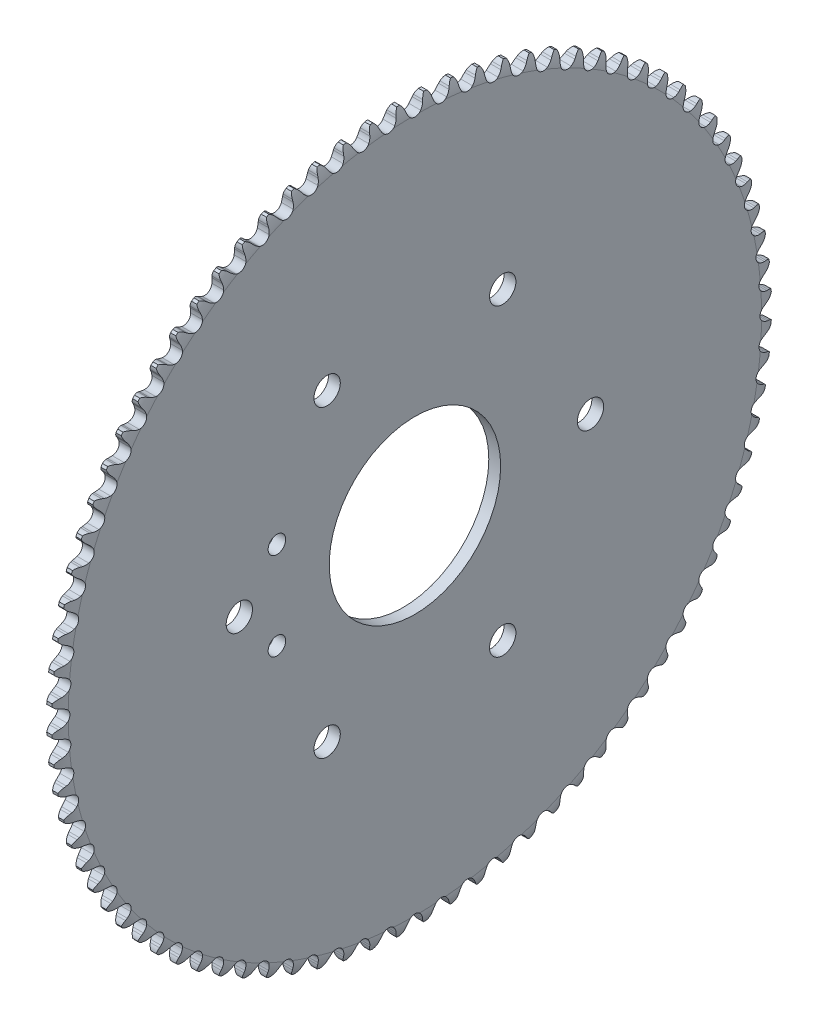
SolidWorks part; units mm, degrees
material "6061 Alloy"
ref_plane "Front Plane" through (0, 0, 0) normal (0, 0, 1) x (1, 0, 0)
ref_plane "Top Plane" through (0, 0, 0) normal (0, 1, 0) x (1, 0, 0)
ref_plane "Right Plane" through (0, 0, 0) normal (1, 0, 0) x (0, 0, -1)
sketch "Sketch1" plane through (0, 0, 0) normal (0, 0, 1) x (1, 0, 0)
  line L0 (-50.8, 0) -> (0, 0) construction
  line L1 (-50.8, 0) -> (-50.8, 125.3628)
  line L2 (-50.8, 0) -> (-46.5115, 0)
  line L3 (-46.5115, 0) -> (-46.5115, 125.3628)
  line L4 (-47.7053, 130.138) -> (-49.6062, 130.138)
  arc A0 (-50.8, 125.3628) -> (-49.6062, 130.138) centre (-40.6527, 125.3628) cw
  arc A1 (-46.5115, 125.3628) -> (-47.7053, 130.138) centre (-56.6588, 125.3628) ccw
  dimension "D6" = 10.1473
  dimension "D1" = 1.1938
  dimension "D2" = 1.1938
  dimension "D3" = 4.7752
  dimension "D4" = 4.7752
  dimension "D5" = 4.2885
  dimension "D7" = 260.276
  dimension "D8" = 50.8
revolve "Revolve1" add sketch "Sketch1" angle 360 about L0
sketch "Sketch2" plane through (-46.5115, 0, 0) normal (1, 0, 0) x (0, 0, -1)
  line L0 (3.0156, 127.6434) -> (3.2609, 128.3817)
  line L1 (0, 0) -> (0, 111.2459) construction
  line L2 (0, 127.3696) -> (-10, 127.3696) construction
  line L3 (-3.0156, 127.6434) -> (-3.2609, 128.3817)
  arc A0 (2.1036, 125.8572) -> (3.0156, 127.6434) centre (-3.2997, 129.7419) ccw
  arc A1 (2.1036, 125.8572) -> (-2.1036, 125.8572) centre (0, 127.3696) cw
  arc A2 (3.2609, 128.3817) -> (7.107, 131.1566) centre (7.107, 127.1036) cw
  arc A3 (-2.1036, 125.8572) -> (-3.0156, 127.6434) centre (3.2997, 129.7419) cw
  arc A4 (-3.2609, 128.3817) -> (-7.107, 131.1566) centre (-7.107, 127.1036) ccw
  arc A5 (7.107, 131.1566) -> (-7.107, 131.1566) centre (0, 0) ccw
  dimension "D2" = 2.5908
  dimension "D4" = 6.6548
  dimension "D7" = 4.0529
  dimension "D1" = 127.3696
  dimension "D6" = 7.107
  dimension "D8" = 0.2659
  dimension "D3" = 35.714
  dimension "D5" = 17.333
extrude "Cut-Extrude1" cut sketch "Sketch2" against normal through all
pattern_circular "CirPattern1" count 85 every 4.286 about axis through (-46.5115, 0, 0) along (-1, 0, 0) of "Cut-Extrude1"
sketch "Sketch3" plane through (-46.5115, 0, 0) normal (1, 0, 0) x (0, 0, -1)
  line L0 (-49.911, 15.875) -> (-49.911, -15.875) construction
  circle A0 centre (0, 0) radius 63.5 construction
  circle A1 centre (-63.5, 0) radius 4.7625
  circle A7 centre (-49.911, 15.875) radius 3.175
  circle A8 centre (-49.911, -15.875) radius 3.175
  circle A9 centre (0, 0) radius 31
  circle A10 centre (-31.75, 54.9926) radius 4.7625
  circle A11 centre (31.75, 54.9926) radius 4.7625
  circle A12 centre (63.5, 0) radius 4.7625
  circle A13 centre (31.75, -54.9926) radius 4.7625
  circle A14 centre (-31.75, -54.9926) radius 4.7625
  point P16 (0, 0)
  point P17 (0, 0)
  point P18 (-49.911, 0)
  point P25 (0, 0)
  dimension "D1" = 127
  dimension "D2" = 9.525
  dimension "D3" = 6.35
  dimension "D6" = 62
  dimension "D4" = 49.911
  dimension "D5" = 31.75
  dimension "D7" = 6
extrude "Cut-Extrude2" cut sketch "Sketch3" against normal through all
